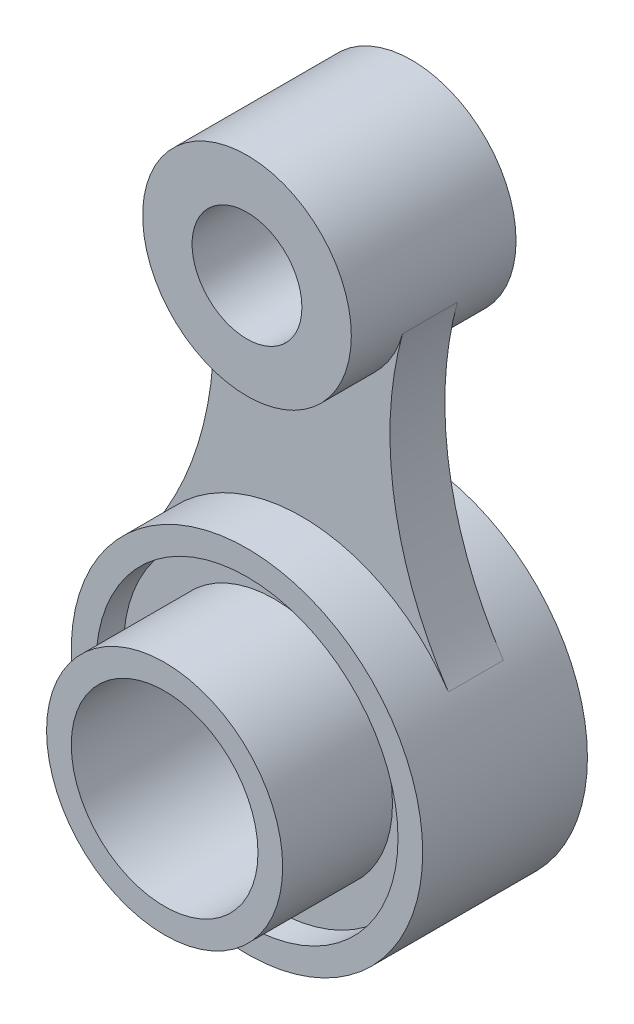
SolidWorks part; units mm, degrees
material "Alliage 1060"
ref_plane "Plan de face" through (0, 0, 0) normal (0, 0, 1) x (1, 0, 0)
ref_plane "Plan de dessus" through (0, 0, 0) normal (0, 1, 0) x (1, 0, 0)
ref_plane "Plan de droite" through (0, 0, 0) normal (1, 0, 0) x (0, 0, -1)
sketch "Esquisse1" plane through (0, 0, 0) normal (0, 0, 1) x (1, 0, 0)
  line L0 (0, 80.1734) -> (0, -40.2761) construction
  line L1 (-68.8765, 0) -> (90.7127, 0) construction
  circle A0 centre (0, 0) radius 17
  circle A1 centre (0, 0) radius 21.5
  circle A2 centre (0, 0) radius 27.5
  circle A3 centre (0, 0) radius 32
  circle A4 centre (0, 75) radius 19
  circle A5 centre (0, 75) radius 10
  arc A6 (-26.6783, 17.6711) -> (-18.3212, 69.9669) centre (-80.0349, 53.0133) ccw
  arc A7 (26.6783, 17.6711) -> (18.3212, 69.9669) centre (80.0349, 53.0133) cw
  dimension "D1" = 64
  dimension "D2" = 55
  dimension "D3" = 43
  dimension "D4" = 34
  dimension "D7" = 38
  dimension "D8" = 20
  dimension "D10" = 64
  dimension "D5" = 0
  dimension "D6" = 0
  dimension "D9" = 75
extrude "Boss.-Extru.1" add sketch "Esquisse1" along normal mid plane 10 contours A3 A7 A4 A6 region at (0, 43.3977, 0)
extrude "Boss.-Extru.2" add sketch "Esquisse1<3>" along normal mid plane 30 contours A4 | A5
sketch "Esquisse1<3>" plane through (0, 0, 0) normal (0, 0, 1) x (1, 0, 0) same geometry as "Esquisse1"
extrude "Boss.-Extru.3" add sketch "Esquisse1<4>" along normal mid plane 30 contours A3 | A0
sketch "Esquisse1<4>" plane through (0, 0, 0) normal (0, 0, 1) x (1, 0, 0) same geometry as "Esquisse1"
extrude "Boss.-Extru.4" add sketch "Esquisse1<5>" along normal blind 30 and the other way blind 15 contours A1 | A0
sketch "Esquisse1<5>" plane through (0, 0, 0) normal (0, 0, 1) x (1, 0, 0) same geometry as "Esquisse1"
extrude "Enlèv. mat.-Extru.1" cut sketch "Esquisse1<6>" against normal blind 5 from offset 15 contours A2 | A1
sketch "Esquisse1<6>" plane through (0, 0, 0) normal (0, 0, 1) x (1, 0, 0) same geometry as "Esquisse1"
